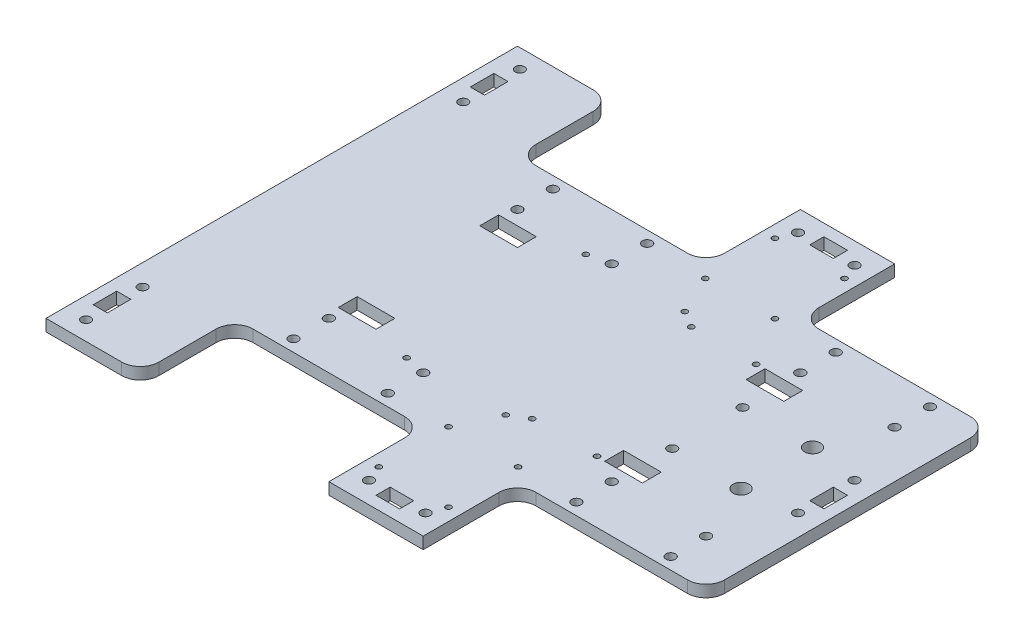
SolidWorks part; units mm, degrees
ref_plane "Front Plane" through (0, 0, 0) normal (0, 0, 1) x (1, 0, 0)
ref_plane "Top Plane" through (0, 0, 0) normal (0, 1, 0) x (1, 0, 0)
ref_plane "Right Plane" through (0, 0, 0) normal (1, 0, 0) x (0, 0, -1)
sketch "Sketch1" plane through (0, 0, 0) normal (0, 1, 0) x (1, 0, 0)
  line L0 (0, 0) -> (0, 152.4) construction
  line L13 (0, 152.4) -> (101.6, 152.4)
  line L16 (152.4, 152.4) -> (254, 152.4)
  line L17 (254, 152.4) -> (254, 0)
  line L18 (254, 0) -> (152.4, 0)
  line L21 (101.6, 0) -> (0, 0)
  line L22 (101.6, 152.4) -> (101.6, 203.2)
  line L23 (101.6, 203.2) -> (152.4, 203.2)
  line L24 (152.4, 203.2) -> (152.4, 152.4)
  line L25 (101.6, 0) -> (101.6, -50.8)
  line L26 (101.6, -50.8) -> (152.4, -50.8)
  line L27 (152.4, -50.8) -> (152.4, 0)
  line L28 (0, 152.4) -> (0, 203.2)
  line L29 (0, 203.2) -> (-50.8, 203.2)
  line L30 (-50.8, 203.2) -> (-50.8, -50.8)
  line L31 (-50.8, -50.8) -> (0, -50.8)
  line L32 (0, -50.8) -> (0, 0)
  dimension "D1" = 254
  dimension "D2" = 152.4
  dimension "D3" = 101.6
  dimension "D4" = 50.8
  dimension "D5" = 50.8
  dimension "D6" = 50.8
  dimension "D7" = 50.8
extrude "Boss-Extrude1" add sketch "Sketch1" along normal blind 6.35
sketch "Sketch2" plane through (0, 6.35, 0) normal (0, 1, 0) x (1, 0, 0)
  line L0 (152.4, 203.2) -> (101.6, 203.2) construction
  line L1 (133.35, 189.23) -> (120.65, 189.23)
  line L2 (133.35, 189.23) -> (133.35, 196.85)
  line L3 (133.35, 196.85) -> (120.65, 196.85)
  line L4 (120.65, 189.23) -> (120.65, 196.85)
  line L5 (254, 0) -> (254, 152.4) construction
  point P6 (127, 203.2)
  dimension "D1" = 12.7
  dimension "D2" = 7.62
  dimension "D3" = 6.35
  dimension "D4" = 19.05
extrude "Cut-Extrude1" cut sketch "Sketch2" against normal through all contours L2 L3 L4 L1
sketch "Sketch3" plane through (0, 0, 0) normal (0, -1, 0) x (1, 0, 0)
  line L0 (0, -76.2) -> (254, -76.2) construction
  line L2 (254, 0) -> (254, -152.4) construction
  line L3 (254, -152.4) -> (152.4, -152.4) construction
  line L4 (101.6, 50.8) -> (152.4, 50.8) construction
  line L5 (127, 50.8) -> (127, -203.2) construction
  line L6 (152.4, -203.2) -> (101.6, -203.2) construction
  line L7 (0, 0) -> (0, -152.4) construction
  line L8 (50.8, 0) -> (50.8, -152.4) construction
  line L9 (0, 0) -> (101.6, 0) construction
  line L10 (101.6, -152.4) -> (0, -152.4) construction
  circle A0 centre (228.6, -146.05) radius 2.54
  circle A1 centre (177.8, -146.05) radius 2.54
  circle A2 centre (228.6, -127) radius 2.54
  circle A3 centre (177.8, -127) radius 2.54
  circle A4 centre (177.8, -25.4) radius 2.54
  circle A5 centre (228.6, -25.4) radius 2.54
  circle A6 centre (177.8, -6.35) radius 2.54
  circle A7 centre (228.6, -6.35) radius 2.54
  circle A8 centre (25.4, -6.35) radius 2.54
  circle A9 centre (76.2, -6.35) radius 2.54
  circle A10 centre (25.4, -25.4) radius 2.54
  circle A11 centre (76.2, -25.4) radius 2.54
  circle A12 centre (76.2, -127) radius 2.54
  circle A13 centre (25.4, -127) radius 2.54
  circle A14 centre (76.2, -146.05) radius 2.54
  circle A15 centre (25.4, -146.05) radius 2.54
  circle A16 centre (142.24, -191.77) radius 2.54
  circle A17 centre (111.76, -191.77) radius 2.54
  circle A18 centre (142.24, 39.37) radius 2.54
  circle A19 centre (111.76, 39.37) radius 2.54
  point P15 (0, -76.2)
  dimension "D1" = 5.08
  dimension "D4" = 5.08
  dimension "D6" = 15.24
  dimension "D2" = 50.8
  dimension "D3" = 25.4
  dimension "D5" = 6.35
  dimension "D7" = 19.05
  dimension "D8" = 11.43
extrude "Cut-Extrude2" cut sketch "Sketch3" against normal through all
hole_wizard "Ø5.0mm Dowel Hole1" positions "3DSketch1" profile "Sketch5" hole size "Ø5.0" standard "ANSI Metric" end condition through all
sketch3d "3DSketch1"
  line L0 (101.6, 6.35, -203.2) -> (101.6, 6.35, -152.4) construction
  line L1 (0, 6.35, -203.2) -> (-50.8, 6.35, -203.2) construction
  line L2 (-50.8, 6.35, 50.8) -> (0, 6.35, 50.8) construction
  line L3 (152.4, 6.35, -203.2) -> (101.6, 6.35, -203.2) construction
  line L4 (-50.8, 6.35, -203.2) -> (-50.8, 6.35, 50.8) construction
  line L5 (254, 6.35, 0) -> (254, 6.35, -152.4) construction
  line L6 (254, 6.35, -152.4) -> (152.4, 6.35, -152.4) construction
  circle A0 centre (142.24, 6.35, -191.77) radius 2.54 construction
  circle A1 centre (111.76, 6.35, -191.77) radius 2.54 construction
  point P0 (-39.37, 6.35, 40.64)
  point P2 (-39.37, 6.35, 10.16)
  point P4 (-39.37, 6.35, -162.56)
  point P6 (-39.37, 6.35, -193.04)
  point P11 (242.57, 6.35, -60.96)
  point P13 (242.57, 6.35, -91.44)
  point P18 (142.24, 3.81, -191.77)
  point P21 (111.76, 3.81, -191.77)
  point P38 (178.4361, 6.35, -95.25)
  point P40 (178.6466, 6.35, -57.1506)
  dimension "D1" = 30.48
  dimension "D5" = 10.16
  dimension "D8" = 11.43
  dimension "D2" = 30.48
  dimension "D3" = 30.48
  dimension "D4" = 30.48
  dimension "D6" = 10.16
  dimension "D7" = 10.16
  dimension "D9" = 11.43
  dimension "D10" = 11.43
  dimension "D11" = 60.96
  dimension "D12" = 38.1
  dimension "D13" = 57.15
sketch "Sketch5" plane through (-39.37, 6.35, 40.64) normal (1, 0, 0) x (0, 0, 1)
  line L0 (0, 0) -> (0, 6.35)
  line L1 (0, 6.35) -> (2.5, 6.35)
  line L2 (2.5, 6.35) -> (2.5, 0)
  line L5 (2.5, 0) -> (0, 0)
  line L11 (0, -6.35) -> (0, 107.95) construction
  dimension "Thru Hole Dia." = 5
  dimension "Thru Hole Depth" = 6.35
sketch "Sketch6" plane through (0, 6.35, 0) normal (0, 1, 0) x (1, 0, 0)
  line L0 (133.35, 189.23) -> (133.35, 196.85) construction
  line L1 (133.35, -44.45) -> (120.65, -44.45)
  line L2 (133.35, -44.45) -> (133.35, -36.83)
  line L3 (133.35, -36.83) -> (120.65, -36.83)
  line L4 (120.65, -44.45) -> (120.65, -36.83)
  line L5 (-44.45, -31.75) -> (-36.83, -31.75)
  line L6 (-44.45, -31.75) -> (-44.45, -19.05)
  line L7 (-44.45, -19.05) -> (-36.83, -19.05)
  line L8 (-36.83, -31.75) -> (-36.83, -19.05)
  line L9 (-44.45, 171.45) -> (-36.83, 171.45)
  line L10 (-44.45, 171.45) -> (-44.45, 184.15)
  line L11 (-44.45, 184.15) -> (-36.83, 184.15)
  line L12 (-36.83, 171.45) -> (-36.83, 184.15)
  line L13 (247.65, 69.85) -> (240.03, 69.85)
  line L14 (247.65, 69.85) -> (247.65, 82.55)
  line L15 (247.65, 82.55) -> (240.03, 82.55)
  line L16 (240.03, 69.85) -> (240.03, 82.55)
  line L17 (133.35, 189.23) -> (120.65, 189.23) construction
  line L18 (-50.8, 203.2) -> (-50.8, -50.8) construction
  line L19 (101.6, -50.8) -> (152.4, -50.8) construction
  line L20 (254, 0) -> (254, 152.4) construction
  line L21 (0, 203.2) -> (-50.8, 203.2) construction
  line L22 (101.6, 0) -> (101.6, -50.8) construction
  line L23 (-50.8, -50.8) -> (0, -50.8) construction
  line L24 (254, 152.4) -> (152.4, 152.4) construction
  point P28 (120.65, -40.64)
  point P33 (0, 0)
  point P34 (0, 0)
  point P35 (0, 0)
  dimension "D1" = 6.35
  dimension "D2" = 6.35
  dimension "D3" = 6.35
  dimension "D4" = 19.05
  dimension "D5" = 19.05
  dimension "D6" = 19.05
  dimension "D7" = 69.85
extrude "Cut-Extrude3" cut sketch "Sketch6" against normal through all
sketch "Sketch7" plane through (0, 6.35, 0) normal (0, 1, 0) x (1, 0, 0)
  line L1 (43.18, 33.02) -> (22.86, 33.02)
  line L2 (43.18, 33.02) -> (43.18, 43.18)
  line L3 (43.18, 43.18) -> (22.86, 43.18)
  line L4 (22.86, 33.02) -> (22.86, 43.18)
  line L5 (43.18, 109.22) -> (22.86, 109.22)
  line L6 (43.18, 109.22) -> (43.18, 119.38)
  line L7 (43.18, 119.38) -> (22.86, 119.38)
  line L8 (22.86, 109.22) -> (22.86, 119.38)
  line L9 (186.69, 33.02) -> (166.37, 33.02)
  line L10 (186.69, 33.02) -> (186.69, 43.18)
  line L11 (186.69, 43.18) -> (166.37, 43.18)
  line L12 (166.37, 33.02) -> (166.37, 43.18)
  line L13 (186.69, 109.22) -> (166.37, 109.22)
  line L14 (186.69, 109.22) -> (186.69, 119.38)
  line L15 (186.69, 119.38) -> (166.37, 119.38)
  line L16 (166.37, 109.22) -> (166.37, 119.38)
  circle A0 centre (25.4, 127) radius 2.54 construction
  circle A1 centre (25.4, 25.4) radius 2.54 construction
  circle A2 centre (177.8, 127) radius 2.54 construction
  dimension "D6" = 2.54
  dimension "D1" = 10.16
  dimension "D2" = 7.62
  dimension "D3" = 20.32
  dimension "D4" = 7.62
  dimension "D5" = 11.43
extrude "Cut-Extrude4" cut sketch "Sketch7" against normal through all
hole_wizard "Ø3.0mm Dowel Hole1" positions "3DSketch2" profile "Sketch8" hole size "Ø3.0" standard "ANSI Metric" end condition through all
sketch3d "3DSketch2"
  line L0 (152.4, 6.35, -203.2) -> (101.6, 6.35, -203.2) construction
  line L1 (101.6, 6.35, 50.8) -> (152.4, 6.35, 50.8) construction
  line L2 (-50.8, 6.35, -203.2) -> (-50.8, 6.35, 50.8) construction
  line L3 (-50.8, 6.35, 50.8) -> (0, 6.35, 50.8) construction
  point P0 (161.925, 6.35, -33.3375)
  point P2 (161.925, 6.35, -119.0625)
  point P4 (127, 6.35, -119.0625)
  point P6 (127, 6.35, -33.3375)
  point P8 (118.11, 6.35, -124.46)
  point P10 (118.11, 6.35, -27.94)
  point P12 (64.77, 6.35, -27.94)
  point P14 (64.77, 6.35, -124.46)
  point P16 (108.1931, 6.35, -182.88)
  point P18 (108.1931, 6.35, -145.38)
  point P20 (145.6931, 6.35, -145.38)
  point P22 (145.6931, 6.35, -182.88)
  point P24 (145.6931, 6.35, 30.48)
  point P26 (108.1931, 6.35, 30.48)
  point P28 (108.1931, 6.35, -7.02)
  point P30 (145.6931, 6.35, -7.02)
  dimension "D1" = 37.5
  dimension "D2" = 37.5
  dimension "D3" = 37.5
  dimension "D4" = 20.32
  dimension "D5" = 20.32
  dimension "D6" = 34.925
  dimension "D7" = 85.725
  dimension "D8" = 96.52
  dimension "D9" = 53.34
  dimension "D10" = 115.57
  dimension "D11" = 78.74
  dimension "D12" = 84.1375
  dimension "D13" = 177.8
sketch "Sketch8" plane through (161.925, 6.35, -33.3375) normal (1, 0, 0) x (0, 0, 1)
  line L0 (0, 0) -> (0, 6.35)
  line L1 (0, 6.35) -> (1.5, 6.35)
  line L2 (1.5, 6.35) -> (1.5, 0)
  line L5 (1.5, 0) -> (0, 0)
  line L11 (0, -6.35) -> (0, 107.95) construction
  dimension "Thru Hole Dia." = 3
  dimension "Thru Hole Depth" = 6.35
hole_wizard "Ø8.0mm Dowel Hole1" positions "3DSketch3" profile "Sketch9" hole size "Ø8.0" standard "ANSI Metric" end condition through all
sketch3d "3DSketch3"
  line L3 (254, 6.35, 0) -> (254, 6.35, -152.4) construction
  line L4 (215.9, 6.35, -56.95) -> (215.9, 6.35, 0) construction
  line L5 (152.4, 6.35, 0) -> (254, 6.35, 0) construction
  line L7 (215.9, 6.35, -95.45) -> (215.9, 6.35, -152.4) construction
  line L8 (254, 6.35, -152.4) -> (152.4, 6.35, -152.4) construction
  point P0 (215.9, 6.35, -56.95)
  point P2 (215.9, 6.35, -95.45)
  point P40 (0, 0, 0)
  dimension "D4" = 38.1
  dimension "D1" = 38.5
sketch "Sketch9" plane through (215.9, 6.35, -56.95) normal (1, 0, 0) x (0, 0, 1)
  line L0 (0, 0) -> (0, 6.35)
  line L1 (0, 6.35) -> (4.25, 6.35)
  line L2 (4.25, 6.35) -> (4.25, 0)
  line L5 (4.25, 0) -> (0, 0)
  line L11 (0, -6.35) -> (0, 107.95) construction
  dimension "Thru Hole Dia." = 8.5
  dimension "Thru Hole Depth" = 6.35
sketch "Sketch10" plane through (0, 6.35, 0) normal (0, 1, 0) x (1, 0, 0)
  line L0 (152.4, 0) -> (254, 0) construction
  line L1 (234.95, 56.261) -> (213.614, 56.261)
  line L2 (234.95, 56.261) -> (234.95, 96.901)
  line L3 (234.95, 96.901) -> (213.614, 96.901)
  line L4 (213.614, 56.261) -> (213.614, 96.901)
  line L5 (240.03, 82.55) -> (240.03, 69.85) construction
  dimension "D1" = 40.64
  dimension "D2" = 21.336
  dimension "D3" = 56.261
  dimension "D4" = 5.08
extrude "Cut-Extrude5" [suppressed] cut sketch "Sketch10" against normal through all
fillet "Fillet1" radius 10 10 edges at (101.6, 3.175, -152.4) (0, 3.175, -203.2) (0, 3.175, -152.4) (0, 3.175, 50.8) (0, 3.175, 0) (101.6, 3.175, 0) (152.4, 3.175, 0) (254, 3.175, 0) (152.4, 3.175, -152.4) (254, 3.175, -152.4)
